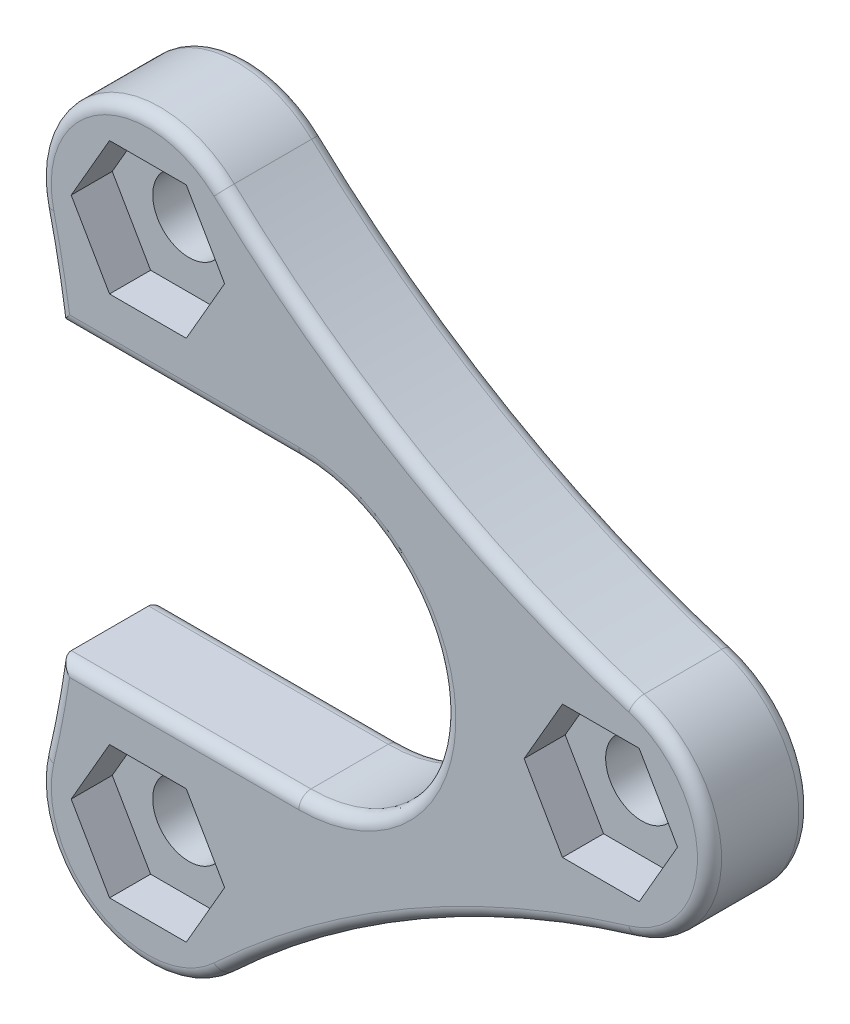
SolidWorks part; units mm, degrees
ref_plane "Front Plane" through (0, 0, 0) normal (0, 0, 1) x (1, 0, 0)
ref_plane "Top Plane" through (0, 0, 0) normal (0, 1, 0) x (1, 0, 0)
ref_plane "Right Plane" through (0, 0, 0) normal (1, 0, 0) x (0, 0, -1)
sketch "Sketch-Reference-Single" plane through (0, 0, 0) normal (0, 0, 1) x (1, 0, 0)
  circle A0 centre (-12.5, 0) radius 1.5
  circle A1 centre (-6.25, 10.8253) radius 1.5
  circle A2 centre (6.25, 10.8253) radius 1.5
  circle A3 centre (12.5, 0) radius 1.5
  circle A4 centre (6.25, -10.8253) radius 1.5
  circle A5 centre (-6.25, -10.8253) radius 1.5
  point P14 (0, 0)
  dimension "D1" = 3
  dimension "D3" = 25
sketch "Sketch-Reference-Dual" plane through (0, 0, 0) normal (0, 0, 1) x (1, 0, 0)
  line L0 (0, 0) -> (-12, 0) construction
  line L1 (0, 0) -> (0, -8.1544) construction
  circle A0 centre (-18, 10.3923) radius 1.5
  circle A1 centre (0, 0) radius 1.5
  circle A2 centre (-18, -10.3923) radius 1.5
  circle A3 centre (18, -10.3923) radius 1.5
  circle A4 centre (18, 10.3923) radius 1.5
  point P11 (-12, 0)
  dimension "D3" = 3
  dimension "D1" = 12
  dimension "D2" = 3
sketch "Sketch1" plane through (0, 0, 0) normal (0, 0, 1) x (1, 0, 0)
  line L0 (0, -8.1544) -> (0, 0) construction
  line L1 (-12, 0) -> (0, 0) construction
  line L2 (-12, 6) -> (-18.9786, 6)
  line L3 (-12, -6) -> (-18.9786, -6)
  line L4 (12, -6) -> (18.9786, -6)
  line L5 (12, 6) -> (18.9786, 6)
  line L6 (0, 0) -> (0, 10.3923) construction
  arc A0 (-12, -6) -> (-12, 6) centre (-12, 0) ccw
  arc A1 (-15.8824, -14.3629) -> (-18.9786, -6) centre (-18, -10.3923) cw
  arc A2 (15.8824, -14.3629) -> (18.9786, -6) centre (18, -10.3923) ccw
  circle A3 centre (-18, 10.3923) radius 4.5
  arc A4 (-15.8824, 14.3629) -> (-18.9786, 6) centre (-18, 10.3923) ccw
  arc A5 (12, -6) -> (12, 6) centre (12, 0) cw
  arc A6 (15.8824, 14.3629) -> (18.9786, 6) centre (18, 10.3923) cw
  arc A7 (-15.8824, 14.3629) -> (15.8824, 14.3629) centre (0, 44.1423) ccw
  arc A8 (-15.8824, -14.3629) -> (15.8824, -14.3629) centre (0, -44.1423) cw
  circle A9 centre (0, 0) radius 1.5 construction
  circle A10 centre (18, -10.3923) radius 1.5 construction
  circle A11 centre (18, 10.3923) radius 1.5 construction
  circle A12 centre (-18, 10.3923) radius 1.5 construction
  circle A13 centre (-18, -10.3923) radius 1.5 construction
  circle A14 centre (0, 0) radius 1.5
  circle A15 centre (18, -10.3923) radius 1.5
  circle A16 centre (18, 10.3923) radius 1.5
  circle A17 centre (-18, 10.3923) radius 1.5
  circle A18 centre (-18, -10.3923) radius 1.5
  dimension "D1" = 12
  dimension "D2" = 3
extrude "Boss-DualMainBody" [suppressed] add sketch "Sketch1" along normal blind 2.5
sketch "Sketch2" [suppressed] plane through (0, 0, 2.5) normal (0, 0, 1) x (1, 0, 0)
  line L0 (0, 0) -> (0, 8.3923) construction
  line L1 (-14.8246, 10.3923) -> (-16.4123, 13.1423)
  line L2 (-16.4123, 13.1423) -> (-19.5877, 13.1423)
  line L3 (-19.5877, 13.1423) -> (-21.1754, 10.3923)
  line L4 (-21.1754, 10.3923) -> (-19.5877, 7.6423)
  line L5 (-19.5877, 7.6423) -> (-16.4123, 7.6423)
  line L6 (-16.4123, 7.6423) -> (-14.8246, 10.3923)
  line L7 (14.8246, 10.3923) -> (16.4123, 7.6423)
  line L8 (16.4123, 7.6423) -> (19.5877, 7.6423)
  line L9 (19.5877, 7.6423) -> (21.1754, 10.3923)
  line L10 (21.1754, 10.3923) -> (19.5877, 13.1423)
  line L11 (19.5877, 13.1423) -> (16.4123, 13.1423)
  line L12 (16.4123, 13.1423) -> (14.8246, 10.3923)
  line L13 (14.8246, -10.3923) -> (16.4123, -13.1423)
  line L14 (16.4123, -13.1423) -> (19.5877, -13.1423)
  line L15 (19.5877, -13.1423) -> (21.1754, -10.3923)
  line L16 (21.1754, -10.3923) -> (19.5877, -7.6423)
  line L17 (19.5877, -7.6423) -> (16.4123, -7.6423)
  line L18 (16.4123, -7.6423) -> (14.8246, -10.3923)
  line L19 (-14.8246, -10.3923) -> (-16.4123, -7.6423)
  line L20 (-16.4123, -7.6423) -> (-19.5877, -7.6423)
  line L21 (-19.5877, -7.6423) -> (-21.1754, -10.3923)
  line L22 (-21.1754, -10.3923) -> (-19.5877, -13.1423)
  line L23 (-19.5877, -13.1423) -> (-16.4123, -13.1423)
  line L24 (-16.4123, -13.1423) -> (-14.8246, -10.3923)
  line L25 (0, 0) -> (-12, 0) construction
  line L27 (0, 3.1754) -> (-2.75, 1.5877)
  line L28 (-12, -6) -> (-18.9786, -6)
  line L29 (18.9786, -6) -> (12, -6)
  line L30 (12, 6) -> (18.9786, 6)
  line L31 (-18.9786, 6) -> (-12, 6)
  line L32 (-12, -6) -> (-18.9786, -6)
  line L33 (18.9786, -6) -> (12, -6)
  line L34 (12, 6) -> (18.9786, 6)
  line L35 (-18.9786, 6) -> (-12, 6)
  line L36 (-2.75, 1.5877) -> (-2.75, -1.5877)
  line L37 (-2.75, -1.5877) -> (0, -3.1754)
  line L38 (0, -3.1754) -> (2.75, -1.5877)
  line L39 (2.75, -1.5877) -> (2.75, 1.5877)
  line L40 (2.75, 1.5877) -> (0, 3.1754)
  circle A0 centre (-18, 10.3923) radius 2.75 construction
  circle A1 centre (18, 10.3923) radius 2.75 construction
  circle A2 centre (18, -10.3923) radius 2.75 construction
  circle A3 centre (-18, -10.3923) radius 2.75 construction
  arc A4 (-15.1249, 13.8541) -> (15.1249, 13.8541) centre (0, 32.0654) ccw
  arc A5 (-15.1249, -13.8541) -> (15.1249, -13.8541) centre (0, -32.0654) cw
  arc A6 (-15.8824, 14.3629) -> (15.8824, 14.3629) centre (0, 44.1423) ccw construction
  circle A7 centre (0, 0) radius 2.75 construction
  arc A12 (-12, -6) -> (-12, 6) centre (-12, 0) ccw
  arc A13 (-18.9786, -6) -> (-15.8824, -14.3629) centre (-18, -10.3923) ccw
  arc A14 (15.8824, -14.3629) -> (-15.8824, -14.3629) centre (0, -44.1423) ccw
  arc A15 (15.8824, -14.3629) -> (18.9786, -6) centre (18, -10.3923) ccw
  arc A16 (12, 6) -> (12, -6) centre (12, 0) ccw
  arc A17 (18.9786, 6) -> (15.8824, 14.3629) centre (18, 10.3923) ccw
  arc A18 (-15.8824, 14.3629) -> (15.8824, 14.3629) centre (0, 44.1423) ccw
  arc A19 (-15.8824, 14.3629) -> (-18.9786, 6) centre (-18, 10.3923) ccw
  arc A20 (-12, -6) -> (-12, 6) centre (-12, 0) ccw
  arc A21 (-18.9786, -6) -> (-15.1249, -13.8541) centre (-18, -10.3923) ccw
  arc A23 (15.1249, -13.8541) -> (18.9786, -6) centre (18, -10.3923) ccw
  arc A24 (12, 6) -> (12, -6) centre (12, 0) ccw
  arc A25 (18.9786, 6) -> (15.1249, 13.8541) centre (18, 10.3923) ccw
  arc A27 (-15.1249, 13.8541) -> (-18.9786, 6) centre (-18, 10.3923) ccw
  point P1 (0, 10.3923)
  dimension "D1" = 5.5
  dimension "D3" = 2
extrude "Boss-DualExtraBody" [suppressed] add sketch "Sketch2" along normal blind 1.7
fillet "Fillet-Dual" [suppressed] radius 0.5
sketch "Sketch3" plane through (0, 0, 0) normal (0, 0, 1) x (1, 0, 0)
  line L0 (0, 0) -> (4.75, 8.2272) construction
  line L1 (0, 6) -> (-9.9207, 6)
  line L2 (0, -6) -> (-9.9207, -6)
  circle A0 centre (-6.25, 10.8253) radius 1.5 construction
  circle A1 centre (12.5, 0) radius 1.5 construction
  circle A2 centre (-6.25, -10.8253) radius 1.5 construction
  circle A3 centre (-6.25, 10.8253) radius 1.5
  circle A4 centre (12.5, 0) radius 1.5
  arc A5 (13.8026, -4.3073) -> (13.8026, 4.3073) centre (12.5, 0) ccw
  circle A6 centre (-6.25, 10.8253) radius 4.5
  arc A7 (-3.1711, 14.1071) -> (-10.6316, 9.7998) centre (-6.25, 10.8253) ccw
  arc A8 (-10.6316, -9.7998) -> (-3.1711, -14.1071) centre (-6.25, -10.8253) ccw
  arc A9 (0, -6) -> (0, 6) centre (0, 0) ccw
  circle A10 centre (-6.25, -10.8253) radius 1.5
  arc A11 (-3.1711, 14.1071) -> (13.8026, 4.3073) centre (26.25, 45.4663) ccw
  arc A12 (13.8026, -4.3073) -> (-3.1711, -14.1071) centre (26.25, -45.4663) ccw
  arc A13 (-10.6316, -9.7998) -> (-9.9207, -6) centre (-52.5, 0) ccw
  arc A14 (-9.9207, 6) -> (-10.6316, 9.7998) centre (-52.5, 0) ccw
  point P30 (0, 0)
  dimension "D1" = 3
  dimension "D2" = 12
  dimension "D3" = 9.5
  dimension "D4" = 3
extrude "Boss-Body" add sketch "Sketch3" along normal blind 2.5
sketch "Sketch4" plane through (0, 0, 2.5) normal (0, 0, 1) x (1, 0, 0)
  line L1 (-4.6623, 13.5753) -> (-7.8377, 13.5753)
  line L2 (0, -6) -> (-9.9207, -6)
  line L3 (-9.9207, 6) -> (0, 6)
  line L4 (0, -6) -> (-9.9207, -6)
  line L5 (-9.9207, 6) -> (0, 6)
  line L6 (-7.8377, 13.5753) -> (-9.4254, 10.8253)
  line L7 (-9.4254, 10.8253) -> (-7.8377, 8.0753)
  line L8 (-7.8377, 8.0753) -> (-4.6623, 8.0753)
  line L9 (-4.6623, 8.0753) -> (-3.0746, 10.8253)
  line L10 (-3.0746, 10.8253) -> (-4.6623, 13.5753)
  line L11 (10.9123, -2.75) -> (14.0877, -2.75)
  line L12 (14.0877, -2.75) -> (15.6754, 0)
  line L13 (15.6754, 0) -> (14.0877, 2.75)
  line L14 (14.0877, 2.75) -> (10.9123, 2.75)
  line L15 (10.9123, 2.75) -> (9.3246, 0)
  line L16 (9.3246, 0) -> (10.9123, -2.75)
  line L17 (-7.8377, -13.5753) -> (-4.6623, -13.5753)
  line L18 (-4.6623, -13.5753) -> (-3.0746, -10.8253)
  line L19 (-3.0746, -10.8253) -> (-4.6623, -8.0753)
  line L20 (-4.6623, -8.0753) -> (-7.8377, -8.0753)
  line L21 (-7.8377, -8.0753) -> (-9.4254, -10.8253)
  line L22 (-9.4254, -10.8253) -> (-7.8377, -13.5753)
  circle A0 centre (-6.25, 10.8253) radius 2.75 construction
  circle A1 centre (12.5, 0) radius 2.75 construction
  circle A2 centre (-6.25, -10.8253) radius 2.75 construction
  arc A8 (0, -6) -> (0, 6) centre (0, 0) ccw
  arc A9 (-10.6316, -9.7998) -> (-9.9207, -6) centre (-52.5, 0) ccw
  arc A10 (-10.6316, -9.7998) -> (-3.1711, -14.1071) centre (-6.25, -10.8253) ccw
  arc A11 (13.8026, -4.3073) -> (-3.1711, -14.1071) centre (26.25, -45.4663) ccw
  arc A12 (13.8026, -4.3073) -> (13.8026, 4.3073) centre (12.5, 0) ccw
  arc A13 (-3.1711, 14.1071) -> (13.8026, 4.3073) centre (26.25, 45.4663) ccw
  arc A14 (-3.1711, 14.1071) -> (-10.6316, 9.7998) centre (-6.25, 10.8253) ccw
  arc A15 (-9.9207, 6) -> (-10.6316, 9.7998) centre (-52.5, 0) ccw
  arc A16 (0, -6) -> (0, 6) centre (0, 0) ccw
  arc A17 (-10.6316, -9.7998) -> (-9.9207, -6) centre (-52.5, 0) ccw
  arc A18 (-10.6316, -9.7998) -> (-3.1711, -14.1071) centre (-6.25, -10.8253) ccw
  arc A19 (13.8026, -4.3073) -> (-3.1711, -14.1071) centre (26.25, -45.4663) ccw
  arc A20 (13.8026, -4.3073) -> (13.8026, 4.3073) centre (12.5, 0) ccw
  arc A21 (-3.1711, 14.1071) -> (13.8026, 4.3073) centre (26.25, 45.4663) ccw
  arc A22 (-3.1711, 14.1071) -> (-10.6316, 9.7998) centre (-6.25, 10.8253) ccw
  arc A23 (-9.9207, 6) -> (-10.6316, 9.7998) centre (-52.5, 0) ccw
  dimension "D2" = 5.5
extrude "Boss-ExtraBody" add sketch "Sketch4" along normal blind 1.7
fillet "Fillet-Single" radius 0.5 20 edges at (-4.9603, 6, 0) (-4.9603, -6, 0) (-4.9603, 6, 4.2) (-4.9603, -6, 4.2) (-10.2334, -7.9079, 0) (-8.5, -14.7224, 0) (-10.2334, 7.9079, 0) (-8.5, 14.7224, 0) (4.75, 8.2272, 0) (17, 0, 0) (-10.2334, -7.9079, 4.2) (-8.5, -14.7224, 4.2) (-10.2334, 7.9079, 4.2) (-8.5, 14.7224, 4.2) (4.75, 8.2272, 4.2) (17, 0, 4.2) (6, 0, 0) (6, 0, 4.2) (4.75, -8.2272, 0) (4.75, -8.2272, 4.2)
equation "\"ScrewSize\"=3"
equation "\"D3@Sketch-Reference-Dual\" = \"ScrewSize\""
equation "\"D1@Sketch-Reference-Single\" = \"ScrewSize\""
equation "\"HotendGrooveDiameter\"=12"
equation "\"D1@Sketch1\"=\"HotendGrooveDiameter\""
equation "\"M3NutSize\"=5.5"
equation "\"D1@Sketch2\"=\"M3NutSize\""
equation "\"HotendGrooveThickness\" = \"HotendGrooveThicknessJHead\" - \"HotendGrooveWiggle\""
equation "\"D1@Boss-DualExtraBody\" = \"HotendGrooveThickness\" - 2.5"
equation "\"HotendGrooveThicknessE3d\"= 6"
equation "\"HotendGrooveThicknessJHead\"= 4.6"
equation "\"HotendGrooveWiggle\"= 0.4"
equation "\"D2@Sketch3\"=\"HotendGrooveDiameter\""
equation "\"D2@Sketch4\"=\"M3NutSize\""
equation "\"D1@Boss-ExtraBody\"=\"HotendGrooveThickness\"-2.5"
